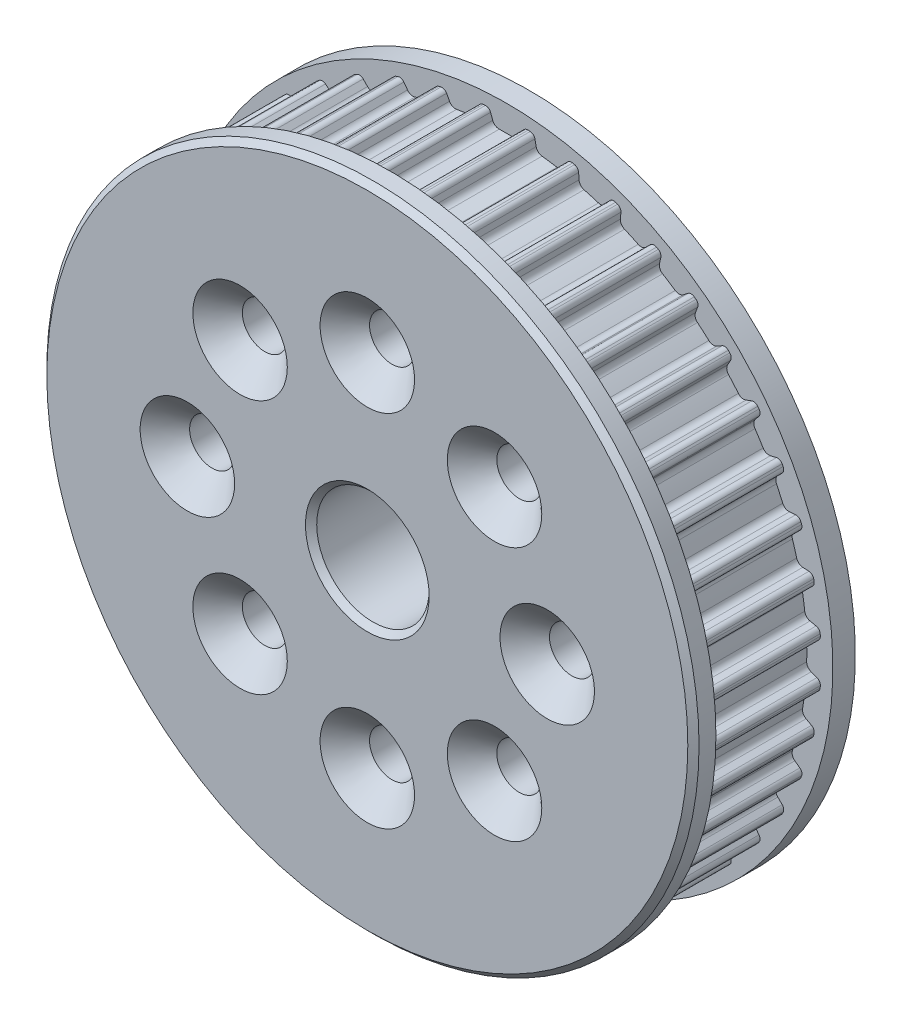
SolidWorks part; units mm, degrees
ref_plane "正面" through (0, 0, 0) normal (0, 0, 1) x (1, 0, 0)
ref_plane "平面" through (0, 0, 0) normal (0, 1, 0) x (1, 0, 0)
ref_plane "右側面" through (0, 0, 0) normal (1, 0, 0) x (0, 0, -1)
sketch "ｽｹｯﾁ1" plane through (0, 0, 0) normal (0, 0, 1) x (1, 0, 0)
  line L0 (-0.7186, 13.7918) -> (-0.6244, 13.5331)
  line L1 (0.6244, 13.5331) -> (0.7186, 13.7918)
  line L2 (0, 0) -> (0, 25.6447) construction
  line L3 (-0.335, 13.3358) -> (0.335, 13.3358) construction
  line L4 (-0.997, 13.9394) -> (0, 0) construction
  line L5 (0, 0) -> (0.997, 13.9394) construction
  line L6 (-0.997, 13.9394) -> (-0.7134, 9.9745)
  line L7 (0.7134, 9.9745) -> (0.997, 13.9394)
  arc A0 (-0.335, 13.3358) -> (0.335, 13.3358) centre (0, 0) cw
  arc A1 (0.9504, 13.9426) -> (0.997, 13.9394) centre (0, 0) cw
  arc A2 (-0.9504, 13.9426) -> (-0.997, 13.9394) centre (0, 0) ccw
  arc A3 (-0.335, 13.3358) -> (-0.6244, 13.5331) centre (-0.3425, 13.6357) cw
  arc A4 (-0.7186, 13.7918) -> (-0.9504, 13.9426) centre (-0.9347, 13.7132) ccw
  arc A5 (0.7186, 13.7918) -> (0.9504, 13.9426) centre (0.9347, 13.7132) cw
  arc A6 (0.335, 13.3358) -> (0.6244, 13.5331) centre (0.3425, 13.6357) ccw
  arc A7 (-0.7134, 9.9745) -> (0.7134, 9.9745) centre (0, 0) ccw
  dimension "D3" = 0.23
  dimension "D4" = 13.975
  dimension "D5" = 0.3
  dimension "D6" = 13.34
  dimension "D10" = 10
  dimension "D1" = 20
  dimension "D2" = 20
  dimension "D7" = 0.67
  dimension "D8" = 4.091
  dimension "D9" = 8.182
extrude "ﾎﾞｽ - 押し出し1" add sketch "ｽｹｯﾁ1" along normal blind 5.2
pattern_circular "円形ﾊﾟﾀｰﾝ1" count 44 over 360 about axis through (0, 0, 5.2) along (0, 0, -1) of "ﾎﾞｽ - 押し出し1"
sketch "ｽｹｯﾁ2" plane through (0, 0, 0) normal (0, 0, -1) x (-1, 0, 0)
  circle A0 centre (0, 0) radius 14.5
  dimension "D1" = 29
extrude "ﾎﾞｽ - 押し出し2" add sketch "ｽｹｯﾁ2" along normal blind 1
sketch "ｽｹｯﾁ3" plane through (0, 0, 5.2) normal (0, 0, 1) x (1, 0, 0)
  circle A0 centre (0, 0) radius 14.5
  circle A1 centre (0, 0) radius 14.5 construction
extrude "ﾎﾞｽ - 押し出し3" add sketch "ｽｹｯﾁ3" along normal blind 1
sketch "ｽｹｯﾁ4" plane through (0, 0, -1) normal (0, 0, -1) x (-1, 0, 0)
  circle A0 centre (0, 0) radius 10
  dimension "D1" = 20
extrude "ﾎﾞｽ - 押し出し4" add sketch "ｽｹｯﾁ4" along normal blind 2.5
sketch "ｽｹｯﾁ5" plane through (0, 0, -3.5) normal (0, 0, -1) x (-1, 0, 0)
  line L0 (0, 0) -> (0, 10) construction
  line L1 (0, 0) -> (7.0711, 7.0711) construction
  line L2 (0, 0) -> (10, 0) construction
  line L3 (0, 0) -> (7.0711, -7.0711) construction
  line L4 (0, 0) -> (0, -10) construction
  line L5 (0, 0) -> (-7.0711, -7.0711) construction
  line L6 (0, 0) -> (-10, 0) construction
  line L7 (0, 0) -> (-7.0711, 7.0711) construction
  circle A0 centre (0, 0) radius 10 construction
  circle A1 centre (0, 8) radius 1
  circle A2 centre (5.6569, 5.6569) radius 1
  circle A3 centre (8, 0) radius 1
  circle A4 centre (5.6569, -5.6569) radius 1
  circle A5 centre (0, -8) radius 1
  circle A6 centre (-5.6569, -5.6569) radius 1
  circle A7 centre (-8, 0) radius 1
  circle A8 centre (-5.6569, 5.6569) radius 1
  circle A9 centre (0, 0) radius 2.5
  point P32 (0, 0)
  dimension "D1" = 2
  dimension "D2" = 8
  dimension "D4" = 5
  dimension "D3" = 8
extrude "ｶｯﾄ - 押し出し1" cut sketch "ｽｹｯﾁ5" against normal through all
chamfer "面取り4" distance 0.5 angle 66 1 edges at (-10, 0, -1) first distance on face at (-10, 0, -1)
chamfer "面取り5" distance 1.1 8 edges at (-1, 8, 6.2) (4.6569, -5.6569, 6.2) (-1, -8, 6.2) (-6.6569, -5.6569, 6.2) (-9, 0, 6.2) (-6.6569, 5.6569, 6.2) (7, 0, 6.2) (4.6569, 5.6569, 6.2)
chamfer "面取り6" distance 0.25 2 edges at (-2.5, 0, 6.2) (14.5, 0, 6.2)
